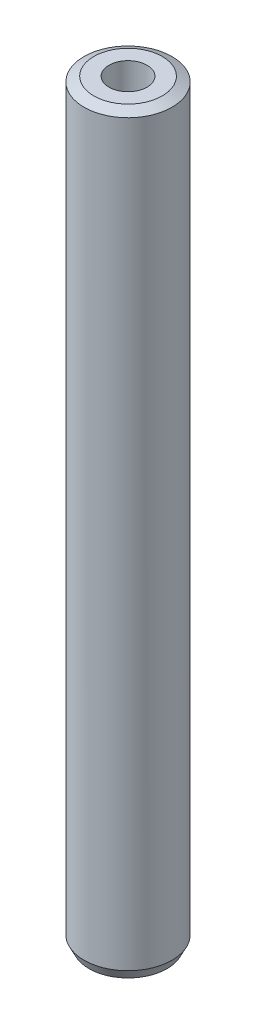
SolidWorks part; units mm, degrees
ref_plane "Front Plane" through (0, 0, 0) normal (0, 0, 1) x (1, 0, 0)
ref_plane "Top Plane" through (0, 0, 0) normal (0, 1, 0) x (1, 0, 0)
ref_plane "Right Plane" through (0, 0, 0) normal (1, 0, 0) x (0, 0, -1)
sketch "Sketch1" plane through (0, 0, 0) normal (0, 1, 0) x (1, 0, 0)
  circle A0 centre (0, 0) radius 5
  dimension "SHAFT_OD" = 10
extrude "Boss-Extrude1" add sketch "Sketch1" along normal blind 85.6603
sketch "Sketch2" plane through (0, 0, 0) normal (0, 1, 0) x (1, 0, 0)
  circle A0 centre (0, 0) radius 2.166
  dimension "BORE_D" = 4.3321
extrude "Cut-Extrude1" cut sketch "Sketch2" along normal through all
chamfer "Chamfer1" distance 0.5592 angle 63.284 2 edges at (0, 85.6603, 5) (0, 0, 5) first distance on face at (0, 85.6603, 5) first distance on face at (0, 0, 2.166)
